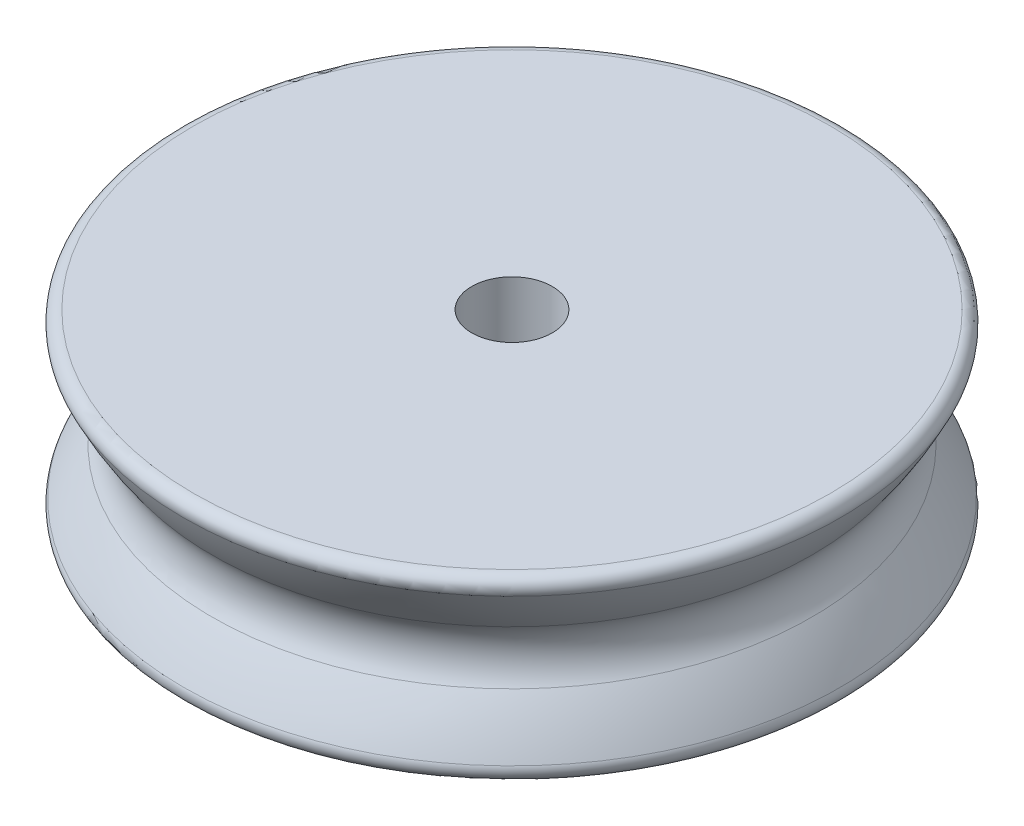
SolidWorks part; units mm, degrees
ref_plane "Front Plane" through (0, 0, 0) normal (0, 0, 1) x (1, 0, 0)
ref_plane "Top Plane" through (0, 0, 0) normal (0, 1, 0) x (1, 0, 0)
ref_plane "Right Plane" through (0, 0, 0) normal (1, 0, 0) x (0, 0, -1)
sketch "Sketch1" plane through (0, 0, 0) normal (0, 0, 1) x (1, 0, 0)
  line L0 (0, 5.08) -> (0, -5.08) construction
  line L1 (2.286, 5.08) -> (2.286, -5.08)
  line L2 (2.286, -5.08) -> (19.05, -5.08)
  line L3 (19.05, -5.08) -> (19.05, -2.54)
  line L4 (0, 0) -> (19.05, 0) construction
  line L5 (19.05, 5.08) -> (19.05, 2.54)
  line L6 (2.286, 5.08) -> (19.05, 5.08)
  arc A0 (19.05, 2.54) -> (19.05, -2.54) centre (19.05, 0) ccw
  point P4 (3.4033, -6.35)
  point P13 (2.286, 0)
  dimension "D5" = 2.54
  dimension "D1" = 10.16
  dimension "D2" = 38.1
  dimension "D4" = 4.572
revolve "Revolve1" add sketch "Sketch1" angle 360 about L0
fillet "Fillet1" radius 16.51 2 edges at (0, -2.54, 19.05) (0, 2.54, 19.05)
fillet "Fillet2" radius 0.635 2 edges at (0, -5.08, 19.05) (0, 5.08, 19.05)
